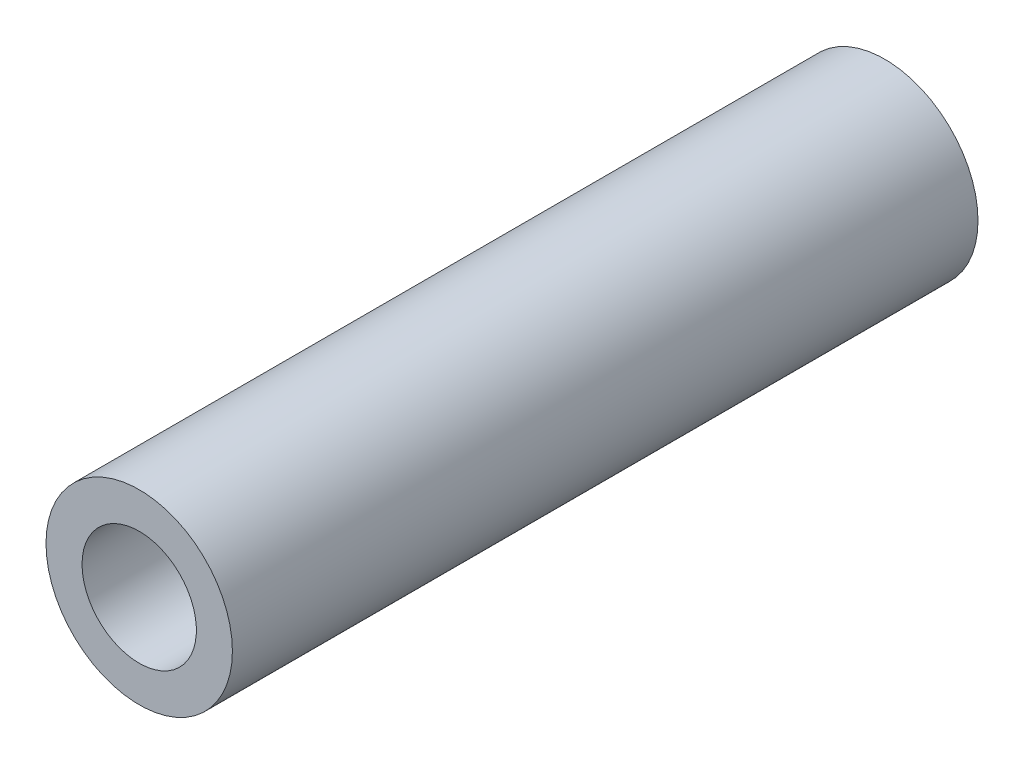
SolidWorks part; units mm, degrees
material "Rubber"
ref_plane "Front Plane" through (0, 0, 0) normal (0, 0, 1) x (1, 0, 0)
ref_plane "Top Plane" through (0, 0, 0) normal (0, 1, 0) x (1, 0, 0)
ref_plane "Right Plane" through (0, 0, 0) normal (1, 0, 0) x (0, 0, -1)
sketch "Sketch1" plane through (0, 0, 0) normal (0, 0, 1) x (1, 0, 0)
  circle A0 centre (0, 0) radius 2.3813
  circle A1 centre (0, 0) radius 1.4605
  dimension "OD" = 4.7625
  dimension "ID" = 2.921
extrude "Extrude1" add sketch "Sketch1" along normal mid plane 19.05
sketch "Sketch2" plane through (0, 0, 0) normal (1, 0, 0) x (0, 0, -1)
  line L0 (-9.525, -1.4605) -> (9.525, -1.4605) construction
  line L3 (9.525, 1.4605) -> (-9.525, 1.4605) construction
  line L5 (-9.525, -1.4605) -> (9.525, -1.4605)
  line L6 (9.525, 1.4605) -> (-9.525, 1.4605)
sketch "Sketch4" plane through (0, 0, 9.525) normal (0, 0, 1) x (1, 0, 0)
  line L0 (0, 0) -> (-1.0327, 1.0327)
  line L1 (0, -2.6194) -> (0, 2.6194) construction
  circle A0 centre (0, 0) radius 1.4605 construction
  dimension "D1" = 45
